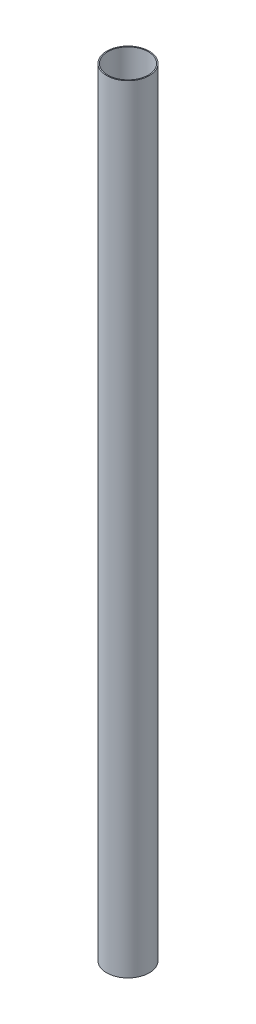
SolidWorks part; units mm, degrees
material "6063-T6"
ref_plane "Front Plane" through (0, 0, 0) normal (0, 0, 1) x (1, 0, 0)
ref_plane "Top Plane" through (0, 0, 0) normal (0, 1, 0) x (1, 0, 0)
ref_plane "Right Plane" through (0, 0, 0) normal (1, 0, 0) x (0, 0, -1)
sketch "Sketch1" plane through (0, 0, 0) normal (0, 1, 0) x (1, 0, 0)
  circle A0 centre (0, 0) radius 24.1554
  circle A1 centre (0, 0) radius 25.4
  dimension "D1" = 50.8
  dimension "D2" = 1.2446
extrude "body" add sketch "Sketch1" along normal blind 927.1
